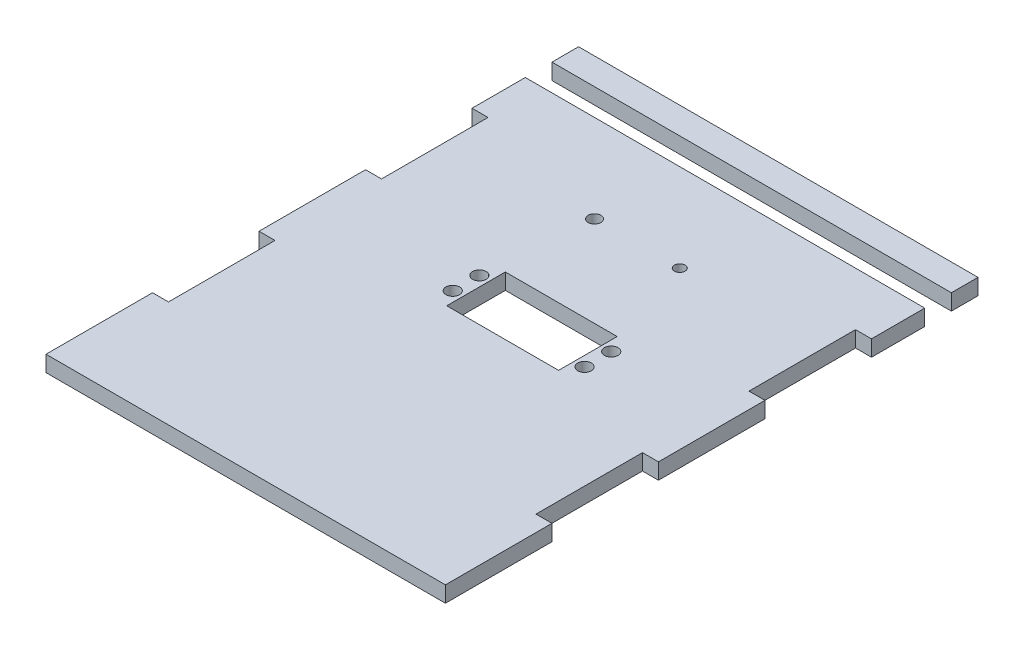
SolidWorks part; units mm, degrees
material "Pine"
ref_plane "Front Plane" through (0, 0, 0) normal (0, 0, 1) x (1, 0, 0)
ref_plane "Top Plane" through (0, 0, 0) normal (0, 1, 0) x (1, 0, 0)
ref_plane "Right Plane" through (0, 0, 0) normal (1, 0, 0) x (0, 0, -1)
sketch "Sketch1" plane through (0, 0, 0) normal (0, 1, 0) x (1, 0, 0)
  line L1 (-75, 100) -> (75, 100)
  line L2 (-75, 100) -> (-75, -100)
  line L3 (-75, -100) -> (75, -100)
  line L4 (75, 100) -> (75, -100)
  line L5 (-75, 100) -> (75, -100) construction
  line L6 (-75, -100) -> (75, 100) construction
  point P0 (0, 0)
  dimension "D1" = 150
  dimension "D2" = 200
extrude "Boss-Extrude1" add sketch "Sketch1" along normal blind 6
sketch "Sketch2" plane through (0, 6, 0) normal (0, 1, 0) x (1, 0, 0)
  line L0 (-75, 100) -> (-75, -100) construction
  line L1 (-75, 60) -> (-69, 60)
  line L2 (-75, 60) -> (-75, 20)
  line L3 (-75, 20) -> (-69, 20)
  line L4 (-69, 60) -> (-69, 20)
  line L5 (75, 100) -> (-75, 100) construction
  line L6 (69, 60) -> (69, 20)
  line L7 (69, 60) -> (75, 60)
  line L8 (75, 60) -> (75, 20)
  line L9 (69, 20) -> (75, 20)
  line L10 (69, -20) -> (69, -60)
  line L11 (69, -20) -> (75, -20)
  line L12 (75, -20) -> (75, -60)
  line L13 (69, -60) -> (75, -60)
  line L14 (-75, -20) -> (-75, -60)
  line L15 (-75, -20) -> (-69, -20)
  line L16 (-69, -20) -> (-69, -60)
  line L17 (-75, -60) -> (-69, -60)
  dimension "D1" = 40
  dimension "D2" = 40
  dimension "D3" = 6
  dimension "D4" = 2
  dimension "D5" = 2
extrude "Cut-Extrude1" cut sketch "Sketch2" against normal blind 6
sketch "Sketch6" plane through (0, 6, 0) normal (0, 1, 0) x (1, 0, 0)
  line L1 (75, -100) -> (75, -60) construction
  circle A0 centre (16, 2) radius 1.23
  dimension "D1" = 2.46
  dimension "D2" = 102
  dimension "D3" = 59
extrude "Cut-Extrude6" cut sketch "Sketch6" against normal through all
sketch "Sketch7" plane through (0, 6, 0) normal (0, 1, 0) x (1, 0, 0)
  line L0 (75, -100) -> (75, -60) construction
  line L1 (-75, -100) -> (75, -100) construction
  circle A0 centre (16, 47) radius 2
  dimension "D1" = 59
  dimension "D2" = 147
extrude "Cut-Extrude7" cut sketch "Sketch7" against normal through all
sketch "Sketch8" plane through (0, 6, 0) normal (0, 1, 0) x (1, 0, 0)
  line L0 (75, 60) -> (75, 100) construction
  line L1 (-75, -100) -> (75, -100) construction
  circle A0 centre (-16, 47) radius 2.38
  dimension "D1" = 91
  dimension "D2" = 147
extrude "Cut-Extrude8" cut sketch "Sketch8" against normal through all
sketch "Sketch9" plane through (0, 6, 0) normal (0, 1, 0) x (1, 0, 0)
  circle A0 centre (30.25, 7) radius 2.55
  circle A1 centre (30.25, -3) radius 2.55
  circle A2 centre (-19.25, 7) radius 2.55
  circle A3 centre (-19.25, -3) radius 2.55
  dimension "D1" = 49.5
  dimension "D2" = 0
  dimension "D3" = 10
  dimension "D4" = 0
  dimension "D5" = 49.5
  dimension "D6" = 0
  dimension "D7" = 93
  dimension "D8" = 55.75
extrude "Cut-Extrude9" cut sketch "Sketch9" against normal through all
sketch "Sketch10" plane through (0, 6, 0) normal (0, 1, 0) x (1, 0, 0)
  line L0 (-75, 100) -> (-75, 60) construction
  line L1 (-75, 90) -> (75, 90)
  line L2 (-75, 90) -> (-75, 80)
  line L3 (-75, 80) -> (75, 80)
  line L4 (75, 90) -> (75, 80)
  line L5 (75, 60) -> (75, 100) construction
  line L6 (75, 100) -> (-75, 100) construction
  dimension "D1" = 10
  dimension "D2" = 10
extrude "Cut-Extrude10" cut sketch "Sketch10" against normal blind 6
extrude "Cut-Extrude11" cut sketch "Sketch11" against normal blind 6
sketch "Sketch11" plane through (0, 6, 0) normal (0, 1, 0) x (1, 0, 0)
  line L1 (-15.5, 13) -> (26.5, 13)
  line L2 (26.5, 13) -> (26.5, -9)
  line L3 (26.5, -9) -> (-15.5, -9)
  line L4 (-15.5, -9) -> (-15.5, 13)
